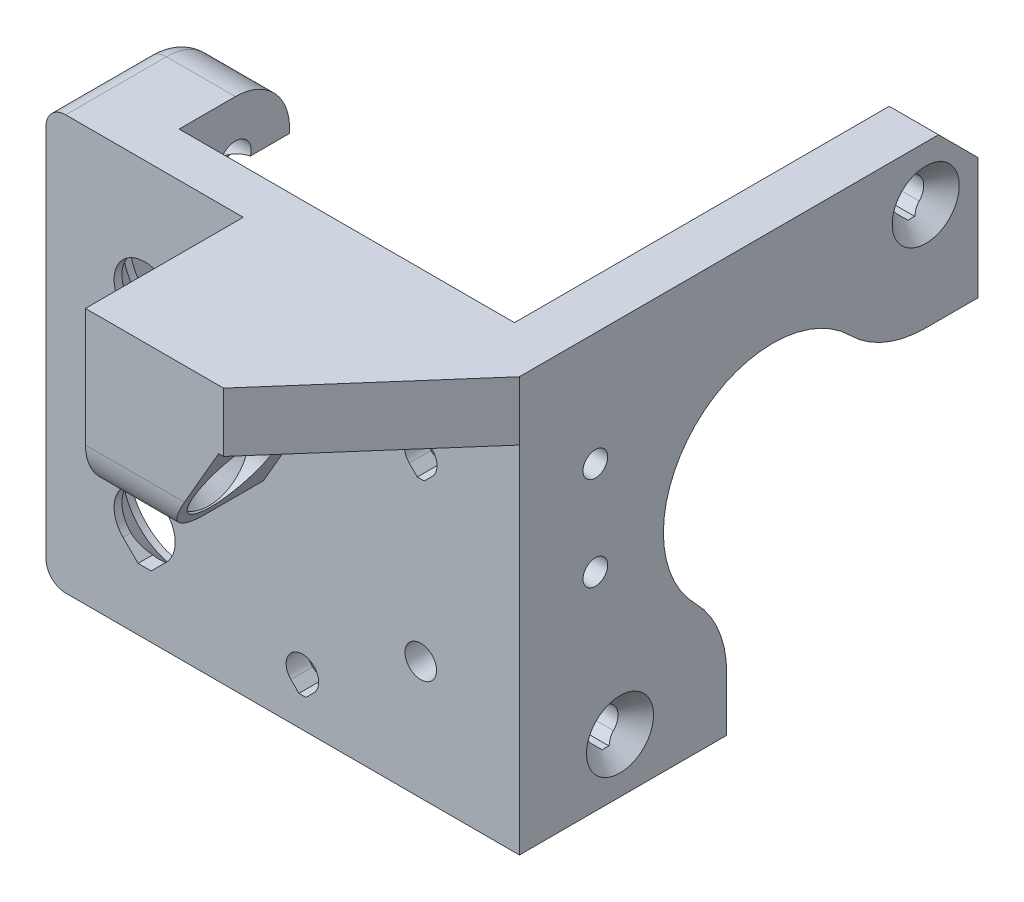
SolidWorks part; units mm, degrees
material "Custom Plastic"
ref_plane "Front Plane" through (0, 0, 0) normal (0, 0, 1) x (1, 0, 0)
ref_plane "Top Plane" through (0, 0, 0) normal (0, 1, 0) x (1, 0, 0)
ref_plane "Right Plane" through (0, 0, 0) normal (1, 0, 0) x (0, 0, -1)
sketch "Sketch1" plane through (0, 0, 0) normal (0, 0, 1) x (1, 0, 0)
  line L0 (-10, -20) -> (-10, 0) construction
  line L1 (-10, -20) -> (10, -20) construction
  line L2 (-10, 0) -> (10, 0) construction
  line L3 (10, -20) -> (10, 0) construction
  line L4 (-10, -20) -> (10, 0) construction
  line L5 (-10, 0) -> (10, -20) construction
  line L6 (-10, 0) -> (-10, 20) construction
  line L7 (-10, 22) -> (-10, -20)
  line L8 (-10, 20) -> (10, 20) construction
  line L9 (10, 0) -> (10, 20) construction
  line L10 (-10, 0) -> (10, 20) construction
  line L11 (-10, 20) -> (10, 0) construction
  line L13 (38, 22) -> (38, -20)
  line L14 (38, 22) -> (-10, 22)
  line L17 (10, -20) -> (38, -20)
  line L18 (10, -20) -> (-10, -20)
  circle A0 centre (0, 10) radius 3.1
  circle A1 centre (0, -10) radius 3.1
  point P0 (0, 10)
  point P1 (0, -10)
  dimension "D2" = 6.2
  dimension "D1" = 20
  dimension "D3" = 38
  dimension "D4" = 42
extrude "Boss-Extrude1" add sketch "Sketch1" along normal blind 4.5
sketch "Sketch4" plane through (0, 0, 4.5) normal (0, 0, 1) x (1, 0, 0)
  line L0 (38, 22) -> (38, 16)
  line L2 (38, -20) -> (38, 22) construction
  line L3 (38, -20) -> (38, 22) construction
  line L4 (38, 22) -> (10, 22)
  line L5 (10, 22) -> (10, 16)
  line L7 (10, 16) -> (38, 16)
  line L8 (38, 22) -> (-10, 22) construction
  dimension "D1" = 6
  dimension "D2" = 28
extrude "Boss-Extrude2" add sketch "Sketch4" along normal blind 16
sketch "Sketch9" plane through (10, 0, 0) normal (-1, 0, 0) x (0, 0, 1)
  line L0 (20.5, 16) -> (20.5, 10)
  line L1 (4.5, 22) -> (20.5, 22) construction
  line L2 (9.6, 5) -> (9.6, 16)
  line L3 (15.5, 5) -> (9.6, 5)
  line L4 (9.6, 16) -> (20.5, 16)
  line L5 (20.5, 16) -> (4.5, 16) construction
  line L7 (4.5, 22) -> (4.5, -20) construction
  arc A0 (20.5, 10) -> (15.5, 5) centre (15.5, 10) cw
  dimension "D3" = 5
  dimension "D1" = 5.1
  dimension "D2" = 12
extrude "Boss-Extrude4" add sketch "Sketch9" against normal blind 6
chamfer "Chamfer8" distance 13 angle 30 1 edges at (16, 16, 15.05) first distance on face at (16, 10.1929, 15.3471)
sketch "Sketch10" plane through (10, 0, 0) normal (-1, 0, 0) x (0, 0, 1)
  circle A0 centre (15.5, 10) radius 2.1
  arc A1 (15.5, 5) -> (20.5, 10) centre (15.5, 10) ccw construction
  dimension "D1" = 4.2
extrude "Cut-Extrude6" cut sketch "Sketch10" against normal up to next
sketch "Sketch11" plane through (10, 0, 0) normal (-1, 0, 0) x (0, 0, 1)
  circle A0 centre (15.5, 10) radius 4.1
  circle A3 centre (15.5, 10) radius 2.1 construction
  dimension "D1" = 8.2
extrude "Cut-Extrude7" cut sketch "Sketch11" against normal up to next from offset 7.5 offset against normal yes
chamfer "Chamfer9" distance 2 angle 45 1 edges at (17.5, 10, 17.6)
sketch "Sketch12" plane through (0, 0, 0) normal (0, 0, -1) x (-1, 0, 0)
  line L1 (-38, 22) -> (-33, 22)
  line L3 (10, 22) -> (1, 22)
  line L4 (10, 22) -> (10, -20)
  line L5 (-38, 22) -> (10, 22) construction
  line L6 (-38, -20) -> (-33, -20)
  line L7 (-38, -20) -> (-38, 22)
  line L8 (1, 22) -> (1, -20)
  line L9 (-33, -20) -> (-33, 22)
  line L11 (1, -20) -> (10, -20)
  line L12 (10, 22) -> (10, -20) construction
  dimension "D1" = 5
  dimension "D2" = 34
extrude "Boss-Extrude5" add sketch "Sketch12" along normal blind 42
sketch "Sketch13" plane through (33, 0, 0) normal (-1, 0, 0) x (0, 0, 1)
  line L1 (-36.7, 16.5) -> (-5.7, 16.5) construction
  line L2 (-36.7, 16.5) -> (-36.7, -14.5) construction
  line L3 (-36.7, -14.5) -> (-5.7, -14.5) construction
  line L4 (-5.7, 16.5) -> (-5.7, -14.5) construction
  line L5 (-36.7, 16.5) -> (-5.7, -14.5) construction
  line L6 (-36.7, -14.5) -> (-5.7, 16.5) construction
  line L7 (-42, -20) -> (4.5, -20) construction
  line L8 (-16.5203, -14.5) -> (-16.5203, -20)
  line L9 (4.5, -20) -> (-42, -20) construction
  line L10 (-16.5203, -20) -> (-42, -20)
  line L11 (-42, -20) -> (-42, 22) construction
  line L12 (-42, -20) -> (-42, 5.6797)
  line L13 (-42, 5.6797) -> (-36.7, 5.6797)
  circle A0 centre (-5.7, -14.5) radius 1.6
  circle A1 centre (-36.7, 16.5) radius 1.6
  arc A2 (-13.3511, -6.8489) -> (-29.0489, 8.8489) centre (-21.2, 1) ccw
  arc A3 (-13.3511, -6.8489) -> (-16.5203, -14.5) centre (-5.7, -14.5) ccw
  arc A4 (-36.7, 5.6797) -> (-29.0489, 8.8489) centre (-36.7, 16.5) ccw
  point P0 (-21.2, 1)
  dimension "D3" = 22.2
  dimension "D4" = 3.2
  dimension "D1" = 31
  dimension "D2" = 21
  dimension "D5" = 21.2
extrude "Cut-Extrude8" cut sketch "Sketch13" against normal through all
sketch "Sketch14" plane through (-10, 0, 0) normal (-1, 0, 0) x (0, 0, 1)
  line L1 (0, 22) -> (0, 12.9343) construction
  line L2 (0, -9.8089) -> (0, -40.8089)
  line L3 (-62, 22) -> (-62, -9.8089)
  line L4 (-5.7, 16.5) -> (-36.7, 16.5) construction
  line L5 (-5.7, -14.5) -> (-5.7, 16.5) construction
  line L6 (4.5, 22) -> (-42, 22) construction
  line L7 (0, -40.8089) -> (-31, -40.8089)
  line L8 (-5.7, 22) -> (-62, 22)
  arc A0 (-5.7, 22) -> (-9.5123, 12.5356) centre (-5.7, 16.5) ccw
  arc A1 (0, -9.8089) -> (-9.5123, 12.5356) centre (-31, -9.8089) ccw
  arc A2 (-62, -9.8089) -> (-31, -40.8089) centre (-31, -9.8089) ccw
  circle A5 centre (-5.7, 16.5) radius 1.6
  circle A6 centre (-5.7, -14.5) radius 1.6 construction
  dimension "D1" = 62
extrude "Cut-Extrude9" cut sketch "Sketch14" against normal up to surface (9 mm away) up to face at (-1, 0.5, -10.5)
chamfer "Chamfer11" distance 16 distance2 14 1 edges at (38, 19, 20.5) first distance on face at (38, 2.2057, -11.8852)
sketch "Sketch16" plane through (0, 0, 4.5) normal (0, 0, 1) x (1, 0, 0)
  circle A0 centre (28, -8) radius 1.6
  dimension "D1" = 3.2
  dimension "D2" = 8
  dimension "D3" = 28
extrude "Cut-Extrude11" cut sketch "Sketch16" against normal up to next
fillet "Fillet1" radius 2 5 edges at (-10, -20, 2.25) (-10, 22, -0.6) (-10, 18.555, -10.8017) (-10, -14.9045, 0) (-10, 2.3336, -2.477)
chamfer "Chamfer13" distance 4 angle 45 1 edges at (35.5, 22, -42) tangent propagation no
chamfer "Chamfer14" distance 1.8 angle 45 2 edges at (38, 14.9, -36.7) (38, -16.1, -5.7)
sketch "Sketch18" plane through (0, 0, 0) normal (0, 0, -1) x (-1, 0, 0)
  circle A0 centre (0, 10) radius 6.1
  circle A1 centre (0, -10) radius 6.1
  dimension "D1" = 12.2
extrude "Cut-Extrude13" cut sketch "Sketch18" against normal blind 0.7 and the other way through all
chamfer "Chamfer15" distance 3 angle 45 2 edges at (-3.1, -10, 0.7) (-3.1, 10, 0.7)
sketch "Sketch20" plane through (0, 0, 4.5) normal (0, 0, 1) x (1, 0, 0)
  line L0 (0, -10) -> (2.192, -12.192)
  line L1 (2.192, -12.192) -> (0.6641, -13.72)
  line L2 (0.6641, -13.72) -> (-0.6641, -13.72)
  line L3 (-0.6641, -13.72) -> (-2.192, -12.192)
  line L4 (-2.192, -12.192) -> (0, -10)
  line L5 (0, -10) -> (0, -13.72) construction
  line L6 (0.6641, 6.28) -> (-0.6641, 6.28)
  line L7 (0, 10) -> (2.192, 7.808)
  line L8 (-0.6641, 6.28) -> (-2.192, 7.808)
  line L9 (-2.192, 7.808) -> (0, 10)
  line L10 (2.192, 7.808) -> (0.6641, 6.28)
  line L11 (0, 10) -> (0, 6.28) construction
  circle A2 centre (0, -10) radius 3.1 construction
  circle A3 centre (0, 10) radius 3.1 construction
  point P5 (0, -13.1)
  point P12 (0, 6.9)
  dimension "D1" = 0.62
  dimension "D2" = 0.62
extrude "Cut-Extrude14" cut sketch "Sketch20" against normal through all
sketch "Sketch21" plane through (-10, 0, 0) normal (-1, 0, 0) x (0, 0, 1)
  line L0 (-5.7, 16.5) -> (-4.5686, 15.3686)
  line L1 (-4.5686, 15.3686) -> (-5.3573, 14.58)
  line L2 (-5.3573, 14.58) -> (-6.0427, 14.58)
  line L3 (-6.0427, 14.58) -> (-6.8314, 15.3686)
  line L4 (-6.8314, 15.3686) -> (-5.7, 16.5)
  line L5 (-5.7, 16.5) -> (-5.7, 14.58) construction
  line L6 (-5.3573, -16.42) -> (-6.0427, -16.42)
  line L7 (-4.5686, -15.6314) -> (-5.3573, -16.42)
  line L8 (-5.7, -14.5) -> (-4.5686, -15.6314)
  line L9 (-5.7, -14.5) -> (-5.7, -16.42) construction
  line L10 (-6.8314, -15.6314) -> (-5.7, -14.5)
  line L11 (-6.0427, -16.42) -> (-6.8314, -15.6314)
  circle A0 centre (-5.7, 16.5) radius 1.6 construction
  circle A2 centre (-5.7, -14.5) radius 1.6 construction
  point P5 (-5.7, 14.9)
  point P15 (-5.7, -16.1)
  dimension "D1" = 0.32
  dimension "D2" = 0.32
extrude "Cut-Extrude15" cut sketch "Sketch21" against normal up to surface (9 mm away) up to face at (-1, 18.5597, -4.9326)
sketch "Sketch23" plane through (33, 0, 0) normal (-1, 0, 0) x (0, 0, 1)
  line L0 (-36.7, 16.5) -> (-37.8314, 15.3686)
  line L1 (-37.8314, 15.3686) -> (-37.0427, 14.58)
  line L2 (-37.0427, 14.58) -> (-36.3573, 14.58)
  line L3 (-36.3573, 14.58) -> (-35.5686, 15.3686)
  line L4 (-35.5686, 15.3686) -> (-36.7, 16.5)
  line L5 (-5.7, -14.5) -> (-6.8314, -15.6314)
  line L6 (-6.8314, -15.6314) -> (-6.0427, -16.42)
  line L7 (-6.0427, -16.42) -> (-5.3573, -16.42)
  line L8 (-5.3573, -16.42) -> (-4.5686, -15.6314)
  line L9 (-4.5686, -15.6314) -> (-5.7, -14.5)
  circle A0 centre (-36.7, 16.5) radius 1.6 construction
  circle A1 centre (-5.7, -14.5) radius 1.6 construction
  point P7 (-36.7, 14.9)
  point P9 (-5.7, -16.1)
  dimension "D1" = 0.32
  dimension "D2" = 0.32
extrude "Cut-Extrude17" cut sketch "Sketch23" against normal through all
sketch "Sketch24" plane through (38, 0, 0) normal (1, 0, 0) x (0, 0, -1)
  line L0 (21.2, 1) -> (3.2, 1) construction
  line L1 (-4.5, -20) -> (-4.5, 16) construction
  circle A0 centre (3.2, 10.5) radius 1.25
  circle A1 centre (3.2, 1) radius 1.25
  dimension "D1" = 2.5
  dimension "D3" = 7.7
  dimension "D2" = 9.5
extrude "Cut-Extrude18" cut sketch "Sketch24" against normal up to surface (5 mm away) up to face at (33, 15.6572, -36.7)
sketch "Sketch25" plane through (0, 0, 0) normal (0, 0, -1) x (-1, 0, 0)
  circle A0 centre (-16, -15) radius 1.65
  circle A1 centre (-28, 10) radius 1.65
  circle A2 centre (-28, -8) radius 1.6 construction
  point P7 (-28, -8)
  dimension "D1" = 3.3
  dimension "D4" = 12
  dimension "D2" = 10
  dimension "D3" = 15
extrude "Cut-Extrude19" cut sketch "Sketch25" against normal up to next
sketch "Sketch26" plane through (0, 0, 0) normal (0, 0, -1) x (-1, 0, 0)
  circle A0 centre (-16, -15) radius 3.4
  circle A1 centre (-28, 10) radius 3.4
  dimension "D1" = 6.8
extrude "Cut-Extrude20" cut sketch "Sketch26" against normal blind 0.5 and the other way through all
chamfer "Chamfer16" distance 1.8 angle 45 2 edges at (26.35, 10, 0.5) (14.35, -15, 0.5)
sketch "Sketch27" plane through (0, 0, 4.5) normal (0, 0, 1) x (1, 0, 0)
  line L0 (16, -15) -> (14.8333, -16.1667)
  line L1 (14.8333, -16.1667) -> (15.6465, -16.98)
  line L2 (15.6465, -16.98) -> (16.3535, -16.98)
  line L3 (16.3535, -16.98) -> (17.1667, -16.1667)
  line L4 (17.1667, -16.1667) -> (16, -15)
  line L5 (26.8333, 8.8333) -> (27.6465, 8.02)
  line L6 (28, 10) -> (26.8333, 8.8333)
  line L7 (27.6465, 8.02) -> (28.3535, 8.02)
  line L8 (28.3535, 8.02) -> (29.1667, 8.8333)
  line L9 (29.1667, 8.8333) -> (28, 10)
  circle A0 centre (16, -15) radius 1.65 construction
  circle A1 centre (28, 10) radius 1.65 construction
  point P8 (16, -16.65)
  point P14 (28, 8.35)
  dimension "D1" = 0.33
  dimension "D2" = 0.33
extrude "Cut-Extrude21" cut sketch "Sketch27" against normal through all
sketch "Sketch28" plane through (0, 0, 0) normal (0, 0, -1) x (-1, 0, 0)
  line L0 (8, -20) -> (-33, -20) construction
  line L1 (0, -20) -> (6.1, -20)
  line L2 (0, -20) -> (0, 10)
  line L3 (0, 10) -> (6.1, 10)
  line L4 (6.1, -20) -> (6.1, 10)
  circle A1 centre (0, 10) radius 6.1 construction
  arc A2 (1, 3.9825) -> (5.548, 12.5356) centre (0, 10) ccw construction
extrude "Cut-Extrude22" cut sketch "Sketch28" along normal through all
chamfer "Chamfer17" distance 1 angle 45 5 edges at (33, -17.25, -16.5203) (33, -10.3592, -15.6967) (33, 8.8489, -13.3511) (33, 6.5033, -32.5592) (33, 5.6797, -39.35)
equation "\"y-cross-rib-thickness\"=4"
equation "\"y-rib-thickness\"=6"
equation "\"bed-plate-thickness\"=3"
equation "\"x-plate-thickness\"=5"
equation "\"rod-diameter\"=12"
equation "\"t-nut-hole-diameter\"=3"
equation "\"y-plate-thickness\"=5"
equation "\"D1@Sketch9\"=\"y-plate-thickness\"+.1"
